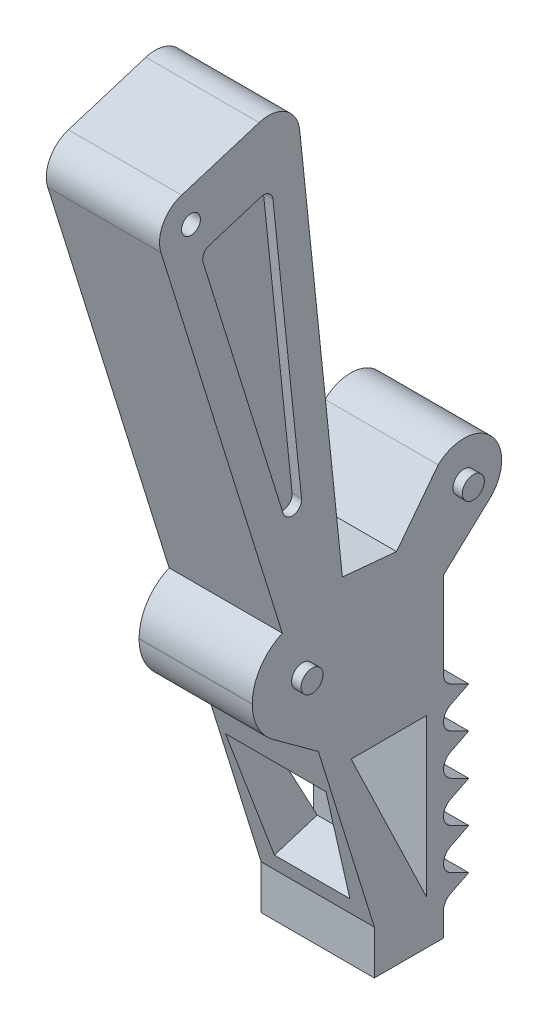
SolidWorks part; units mm, degrees
material "6061-T6 (SS)"
ref_plane "Front Plane" through (0, 0, 0) normal (0, 0, 1) x (1, 0, 0)
ref_plane "Top Plane" through (0, 0, 0) normal (0, 1, 0) x (1, 0, 0)
ref_plane "Right Plane" through (0, 0, 0) normal (1, 0, 0) x (0, 0, -1)
sketch "Sketch1" plane through (0, 0, 0) normal (1, 0, 0) x (0, 0, -1)
  line L0 (52.963, 0) -> (32.1782, 66.843)
  line L1 (32.1782, 66.843) -> (55.0958, 73.9693)
  line L2 (55.0958, 73.9693) -> (62.512, 2.9693)
  line L3 (62.512, 2.9693) -> (52.963, 0)
  line L4 (52.963, 0) -> (48.1885, -1.4846)
  line L5 (48.1885, -1.4846) -> (48.1885, -11.4846)
  line L6 (48.1885, -11.4846) -> (58.6915, -19.1454)
  line L7 (58.6915, -19.1454) -> (67.5993, -47.7924)
  line L8 (67.5993, -47.7924) -> (67.5993, -54.7924)
  line L9 (67.5993, -54.7924) -> (78.5993, -54.7924)
  line L10 (78.5993, -54.7924) -> (78.5993, -4.7924)
  line L11 (78.5993, -4.7924) -> (85.9225, 2.0171)
  line L12 (62.512, 2.9693) -> (71.1295, 2.1577)
  line L13 (85.9225, 2.0171) -> (77.7511, 10.805) construction
  line L14 (71.1295, 2.1577) -> (77.7511, 10.805)
  arc A1 (85.9225, 2.0171) -> (77.7511, 10.805) centre (81.8368, 6.4111) ccw
  dimension "D1" = 70
  dimension "D2" = 24
  dimension "D3" = 71
  dimension "D4" = 10
  dimension "D5" = 15
  dimension "D6" = 10
  dimension "D7" = 13
  dimension "D8" = 30
  dimension "D9" = 7
  dimension "D10" = 11
  dimension "D11" = 50
  dimension "D12" = 12
  dimension "D13" = 10
extrude "Boss-Extrude1" add sketch "Sketch1" along normal mid plane 18 contours L11 L13 L14 L12 L3 L4 L5 L6 L7 L8 L9 L10 | L3 L2 L1 L0 | L13 A1 region at (0, 40.6753, -49.7196) region at (0, -18.9068, -68.4608) region at (0, 8.1451, -83.7016)
sketch "Sketch2" plane through (9, 0, 0) normal (1, 0, 0) x (0, 0, -1)
  line L0 (75.8993, -47.7924) -> (75.8993, -22.7924)
  line L1 (75.8993, -22.7924) -> (63.8993, -22.7924)
  line L2 (63.8993, -22.7924) -> (75.8993, -47.7924)
  line L3 (78.5993, -54.7924) -> (78.5993, -4.7924) construction
  line L4 (67.5993, -47.7924) -> (78.5993, -47.7924) construction
  dimension "D1" = 25
  dimension "D2" = 12
  dimension "D3" = 2.7
extrude "Cut-Extrude1" cut sketch "Sketch2" against normal blind 25
sketch "Sketch3" plane through (9, 0, 0) normal (1, 0, 0) x (0, 0, -1)
  line L0 (78.5993, -49.7924) -> (78.5993, -47.7924)
  line L1 (78.5993, -54.7924) -> (78.5993, -4.7924) construction
  line L2 (78.5993, -47.7924) -> (82.5993, -47.7924)
  line L3 (82.5993, -47.7924) -> (78.5993, -49.7924)
  line L4 (82.5993, -47.7924) -> (78.5993, -45.7924)
  line L5 (78.5993, -45.7924) -> (78.5993, -47.7924)
  line M19 (78.5993, -54.7924) -> (78.5993, -4.7924)
  dimension "D1" = 4
  dimension "D2" = 2
  dimension "D3" = 4
  dimension "D4" = 5
extrude "Boss-Extrude2" add sketch "Sketch3" against normal up to surface (18 mm away) contours L3 L2 M19 | L2 L4 M19 region at (9, -48.4591, -79.9326) region at (9, -47.1258, -79.9326) up to face at (-9, -31.1258, -71.8993)
fillet "Fillet1" radius 2 2 edges at (0, -49.7924, -78.5993) (0, -45.7924, -78.5993)
pattern_linear "LPattern1" count 5 spacing 6.5 along (0, 1, 0) of "Fillet1", "Boss-Extrude2"
fillet "Fillet2" radius 8 2 edges at (0, -11.4846, -48.1885) (0, -1.4846, -48.1885)
fillet "Fillet3" radius 5 2 edges at (0, 73.9693, -55.0958) (0, 66.843, -32.1782)
sketch "Sketch4" plane through (9, 0, 0) normal (1, 0, 0) x (0, 0, -1)
  circle A0 centre (38.4373, 63.5532) radius 1.5
  dimension "D1" = 3
extrude "Cut-Extrude2" cut sketch "Sketch4" against normal blind 25
sketch "Sketch5" plane through (0, 14.9531, -48.0886) normal (0, -0.2969, 0.9549) x (1, 0, 0)
  line L0 (0, -35.709) -> (0, -65.709) construction
  line L1 (9, -35.709) -> (-9, -35.709) construction
  line L2 (9, -65.709) -> (-9, -65.709) construction
  line L3 (-8, -43.209) -> (8, -43.209)
  line L5 (-6, -62.709) -> (6, -62.709)
  line L6 (-8, -43.209) -> (-6, -62.709)
  line L7 (6, -62.709) -> (8, -43.209)
  point P6 (0, -43.209)
  point P10 (0, -43.209)
  point P12 (0, -62.709)
  dimension "D1" = 7.5
  dimension "D2" = 16
  dimension "D3" = 12
  dimension "D4" = 3
extrude "Cut-Extrude3" cut sketch "Sketch5" against normal blind 8
sketch "Sketch6" plane through (9, 0, 0) normal (1, 0, 0) x (0, 0, -1)
  circle A0 centre (81.8368, 6.4111) radius 1.75
  dimension "D1" = 3.5
extrude "Boss-Extrude3" add sketch "Sketch6" along normal blind 1.5
sketch "Sketch7" plane through (9, 0, 0) normal (1, 0, 0) x (0, 0, -1)
  circle A0 centre (56.1885, -7.4178) radius 1.75
  dimension "D1" = 3.5
extrude "Boss-Extrude4" add sketch "Sketch7" along normal blind 1.5
sketch "Sketch8" plane through (9, 0, 0) normal (1, 0, 0) x (0, 0, -1)
  line L0 (41.3543, 59.2241) -> (49.539, 61.7691)
  line L1 (36.9527, 68.3277) -> (49.2719, 72.1583) construction
  line L2 (51.4763, 60.4926) -> (56.0168, 17.024)
  line L3 (55.7294, 67.9032) -> (62.512, 2.9693) construction
  line L4 (40.3674, 57.3463) -> (53.0925, 16.4227)
  line L5 (52.963, 0) -> (33.6628, 62.0685) construction
  arc A0 (56.0168, 17.024) -> (53.0925, 16.4227) centre (54.5249, 16.8681) cw
  arc A1 (49.539, 61.7691) -> (51.4763, 60.4926) centre (49.9844, 60.3367) cw
  arc A2 (41.3543, 59.2241) -> (40.3674, 57.3463) centre (41.7997, 57.7917) ccw
  dimension "D4" = 1.5
  dimension "D1" = 5
  dimension "D2" = 5
  dimension "D3" = 10
extrude "Cut-Extrude4" cut sketch "Sketch8" against normal blind 1.5
mirror "Mirror1" about plane through (0, 0, 0) normal (1, 0, 0) of "Boss-Extrude3", "Boss-Extrude4", "Cut-Extrude4"
